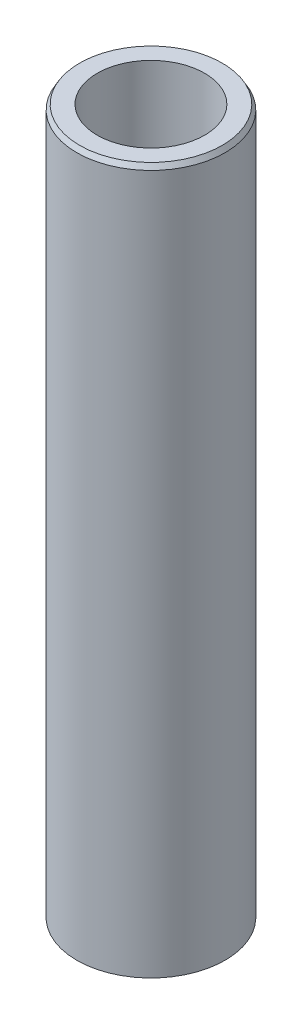
SolidWorks part; units mm, degrees
ref_plane "Front Plane" through (0, 0, 0) normal (0, 0, 1) x (1, 0, 0)
ref_plane "Top Plane" through (0, 0, 0) normal (0, 1, 0) x (1, 0, 0)
ref_plane "Right Plane" through (0, 0, 0) normal (1, 0, 0) x (0, 0, -1)
sketch "Sketch1" plane through (0, 0, 0) normal (0, 1, 0) x (1, 0, 0)
  circle A0 centre (0, 0) radius 40
  dimension "SHAFT_OD" = 80
extrude "Boss-Extrude1" add sketch "Sketch1" along normal blind 381.4346
sketch "Sketch2" plane through (0, 0, 0) normal (0, 1, 0) x (1, 0, 0)
  circle A0 centre (0, 0) radius 28.973
  dimension "BORE_D" = 57.946
extrude "Cut-Extrude1" cut sketch "Sketch2" along normal through all
chamfer "Chamfer1" distance 2.6597 angle 30 2 edges at (0, 381.4346, 40) (0, 0, 40) first distance on face at (0, 381.4346, 40) first distance on face at (0, 0, 28.973)
